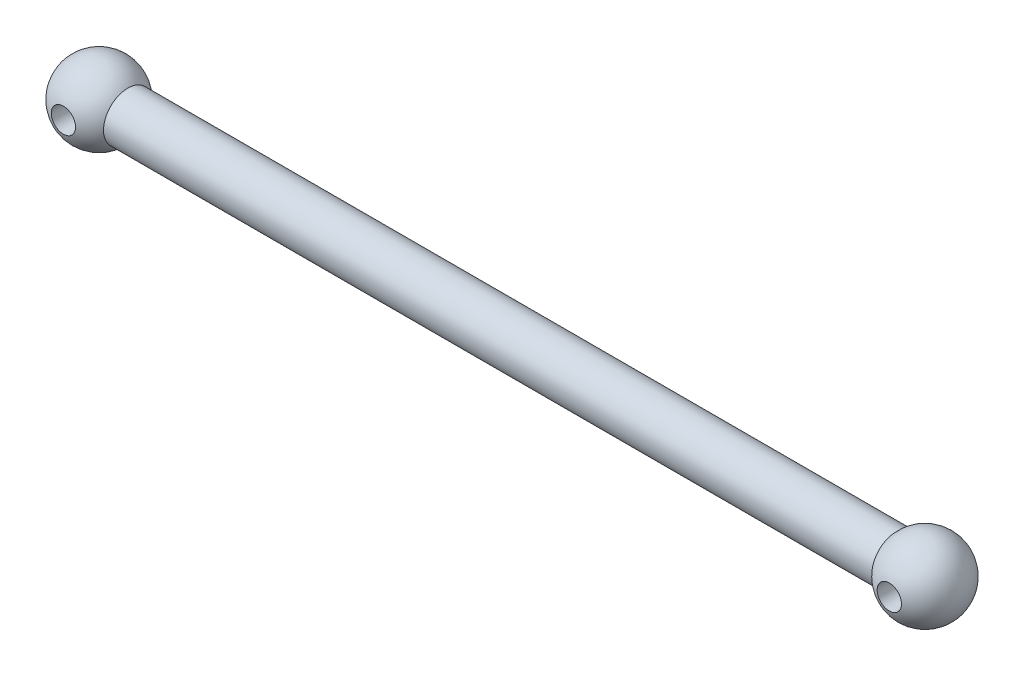
SolidWorks part; units mm, degrees
ref_plane "Front Plane" through (0, 0, 0) normal (0, 0, 1) x (1, 0, 0)
ref_plane "Top Plane" through (0, 0, 0) normal (0, 1, 0) x (1, 0, 0)
ref_plane "Right Plane" through (0, 0, 0) normal (1, 0, 0) x (0, 0, -1)
sketch "Sketch1" plane through (0, 0, 0) normal (0, 1, 0) x (1, 0, 0)
  line L0 (-31.6315, 2) -> (31.6315, 2)
  line L1 (-34, 0) -> (34, 0) construction
  line L2 (-31.6315, -2) -> (31.6315, -2)
  line L3 (-30.9, 0) -> (-37.1, 0)
  line L4 (30.9, 0) -> (37.1, 0)
  circle A0 centre (-34, 0) radius 3.1
  circle A1 centre (34, 0) radius 3.1
  point P13 (0, 0)
  dimension "D1" = 6.2
  dimension "D2" = 2
  dimension "D3" = 2
  dimension "D4" = 68
revolve "Revolve2" add sketch "Sketch1" angle 360 about L1 region at (-34, 0, 1.3157) region at (0, 0, 1.0038) region at (34, 0, 1.3157)
sketch "Sketch2" plane through (0, 0, 0) normal (0, 0, 1) x (1, 0, 0)
  line L0 (0, -3.41) -> (0, 3.41) construction
  circle A2 centre (34, 0) radius 1
  circle A3 centre (-34, 0) radius 1
  point P2 (28.7859, 0)
  point P3 (30.1966, 0)
  point P4 (0, 0)
  point P6 (30.1929, 0)
  dimension "D1" = 2
  dimension "D2" = 34
extrude "Cut-Extrude1" cut sketch "Sketch2" against normal through all both and the other way through all
